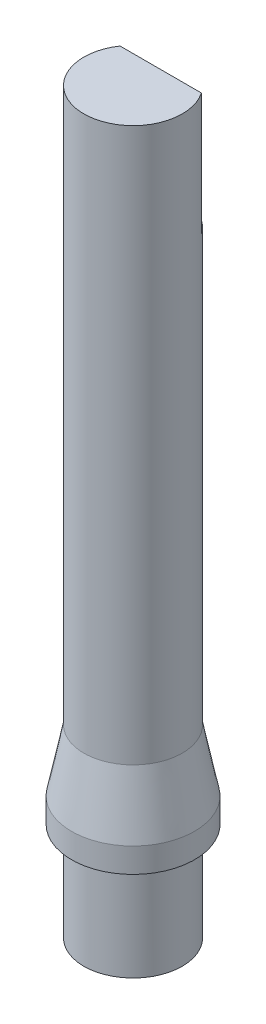
SolidWorks part; units mm, degrees
ref_plane "Front Plane" through (0, 0, 0) normal (0, 0, 1) x (1, 0, 0)
ref_plane "Top Plane" through (0, 0, 0) normal (0, 1, 0) x (1, 0, 0)
ref_plane "Right Plane" through (0, 0, 0) normal (1, 0, 0) x (0, 0, -1)
sketch "Sketch1" plane through (0, 0, 0) normal (0, 1, 0) x (1, 0, 0)
  circle A0 centre (0, 0) radius 4
  dimension "D1" = 8
extrude "Boss-Extrude1" add sketch "Sketch1" along normal blind 60
ref_plane "Plane1" through (0, 8, 0) normal (0, -1, 0) x (-1, 0, 0)
sketch "Sketch2" plane through (0, 8, 0) normal (0, -1, 0) x (-1, 0, 0)
  circle A0 centre (0, 0) radius 5
  circle A1 centre (0, 0) radius 4 construction
  dimension "D1" = 10
extrude "Boss-Extrude2" add sketch "Sketch2" against normal blind 2
chamfer "Chamfer1" distance 5 distance2 1 1 edges at (0, 10, -4) first distance on face at (0, 60, 4)
sketch "Sketch3" plane through (0, 60, 0) normal (0, 1, 0) x (1, 0, 0)
  line L0 (-3.3072, 2.25) -> (3.3072, 2.25)
  circle A0 centre (0, 0) radius 4 construction
  arc A1 (3.3072, 2.25) -> (-3.3072, 2.25) centre (0, 0) ccw
  point P4 (0, 4)
  point P8 (0, 0)
  dimension "D1" = 1.75
extrude "Cut-Extrude1" cut sketch "Sketch3" against normal blind 10
